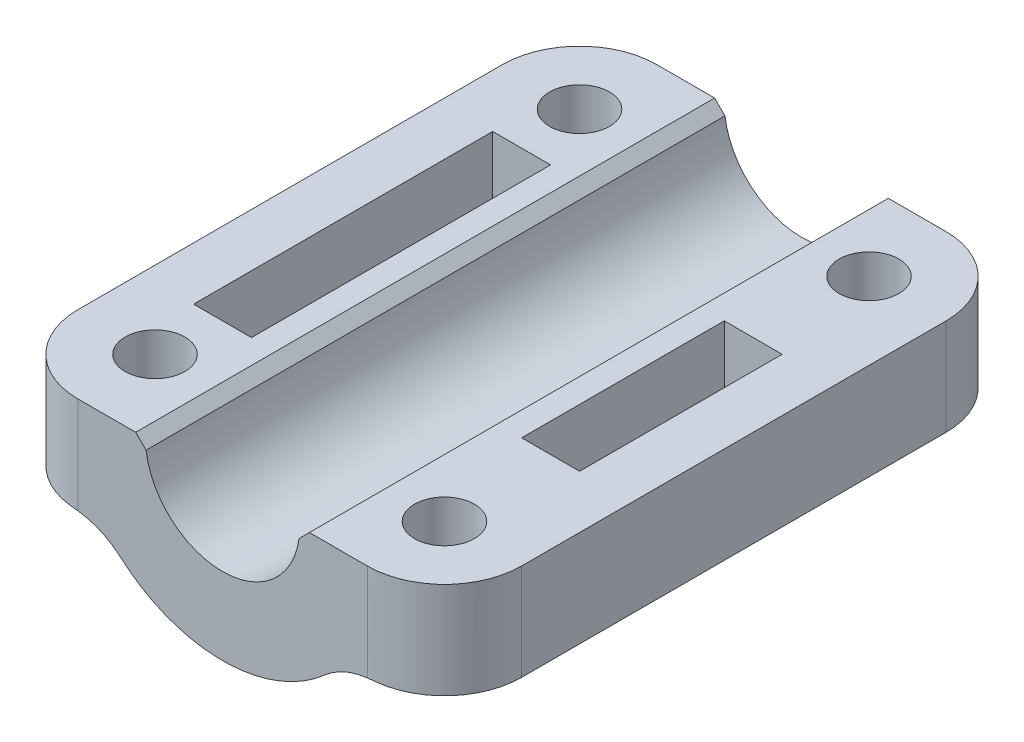
SolidWorks part; units mm, degrees
ref_plane "Front" through (0, 0, 0) normal (0, 0, 1) x (1, 0, 0)
ref_plane "Top" through (0, 0, 0) normal (0, 1, 0) x (1, 0, 0)
ref_plane "Right" through (0, 0, 0) normal (1, 0, 0) x (0, 0, -1)
sketch "Sketch1" plane through (0, 0, 0) normal (0, 1, 0) x (1, 0, 0)
  line L1 (-7.5, -11) -> (7.5, -11) construction
  line L2 (-7.5, -11) -> (-7.5, 11) construction
  line L3 (-7.5, 11) -> (7.5, 11) construction
  line L4 (7.5, -11) -> (7.5, 11) construction
  line L5 (-7.5, -11) -> (7.5, 11) construction
  line L6 (-7.5, 11) -> (7.5, -11) construction
  line L7 (-11.5, -15) -> (11.5, -15)
  line L8 (-11.5, -15) -> (-11.5, 15)
  line L9 (-11.5, 15) -> (11.5, 15)
  line L10 (11.5, -15) -> (11.5, 15)
  line L11 (-11.5, -15) -> (11.5, 15) construction
  line L12 (-11.5, 15) -> (11.5, -15) construction
  circle A0 centre (-7.5, 11) radius 1.55
  circle A1 centre (7.5, 11) radius 1.55
  circle A2 centre (7.5, -11) radius 1.55
  circle A3 centre (-7.5, -11) radius 1.55
  point P0 (0, 0)
  point P10 (0, 0)
  dimension "D3" = 3.1
  dimension "D1" = 15
  dimension "D2" = 22
  dimension "D4" = 4
  dimension "D5" = 4
extrude "Boss-Extrude1" add sketch "Sketch1" along normal blind 5
fillet "Fillet1" radius 4 4 edges at (11.5, 2.5, 15) (-11.5, 2.5, 15) (-11.5, 2.5, -15) (11.5, 2.5, -15)
sketch "Sketch3" plane through (0, 0, -15) normal (0, 0, -1) x (-1, 0, 0)
  line L1 (-7.5, 5) -> (7.5, 5) construction
  circle A0 centre (0, 5) radius 4
  dimension "D1" = 8
extrude "Cut-Extrude1" cut sketch "Sketch3" against normal up to next
sketch "Sketch4" plane through (0, 0, -15) normal (0, 0, -1) x (-1, 0, 0)
  circle A0 centre (0, 5) radius 8
  arc A1 (-4, 5) -> (4, 5) centre (0, 5) ccw construction
  line M6 (-7.5, 0) -> (7.5, 0)
  dimension "D1" = 4
extrude "Boss-Extrude3" add sketch "Sketch4" against normal up to surface (30 mm away) contours A0 M6 region at (0, -1.2217, -15) up to face at (0, 2.6667, 15)
extrude "Cut-Extrude2" cut sketch "Sketch1<2>" against normal up to next contours A1 | A0 | A3 | A2 region at (-7.5, 0, -11) region at (7.5, 0, -11) region at (7.5, 0, 11) region at (-7.5, 0, 11)
sketch "Sketch1<2>" plane through (0, 0, 0) normal (0, 1, 0) x (1, 0, 0) same geometry as "Sketch1"
sketch "Sketch5" plane through (0, 0, 0) normal (0, -1, 0) x (1, 0, 0)
  circle A0 centre (-7.5, 11) radius 2.75
  circle A1 centre (7.5, 11) radius 2.75
  circle A2 centre (7.5, -11) radius 2.75
  circle A3 centre (-7.5, -11) radius 2.75
  dimension "D1" = 5.5
extrude "Cut-Extrude3" cut sketch "Sketch5" along normal up to next
fillet "Fillet2" radius 4 6 edges at (6.245, 0, -14.2235) (-6.245, 0, -14.2235) (-6.245, 0, 14.2235) (6.245, 0, 14.2235) (6.245, 0, 0) (-6.245, 0, 0)
chamfer "Chamfer1" distance 0.5 angle 45 2 edges at (4, 5, 0) (-4, 5, 0)
sketch "Sketch6" plane through (0, 5, 0) normal (0, 1, 0) x (1, 0, 0)
  line L1 (-8.75, -7.75) -> (-5.75, -7.75)
  line L2 (-8.75, -7.75) -> (-8.75, 7.75)
  line L3 (-8.75, 7.75) -> (-5.75, 7.75)
  line L4 (-5.75, -7.75) -> (-5.75, 7.75)
  line L5 (-8.75, -7.75) -> (-5.75, 7.75) construction
  line L6 (-8.75, 7.75) -> (-5.75, -7.75) construction
  line L7 (0, 0) -> (0, 15.2619) construction
  line L9 (5.75, -5.25) -> (8.75, -5.25)
  line L10 (5.75, -5.25) -> (5.75, 5.25)
  line L11 (5.75, 5.25) -> (8.75, 5.25)
  line L12 (8.75, -5.25) -> (8.75, 5.25)
  line L13 (5.75, -5.25) -> (8.75, 5.25) construction
  line L14 (5.75, 5.25) -> (8.75, -5.25) construction
  point P0 (-7.25, 0)
  point P6 (7.25, 0)
  point P13 (6.5096, 0)
  dimension "D1" = 15.5
  dimension "D2" = 3
  dimension "D3" = 7.25
  dimension "D4" = 3
  dimension "D5" = 10.5
  dimension "D6" = 7.25
extrude "Cut-Extrude4" cut sketch "Sketch6" against normal up to next
